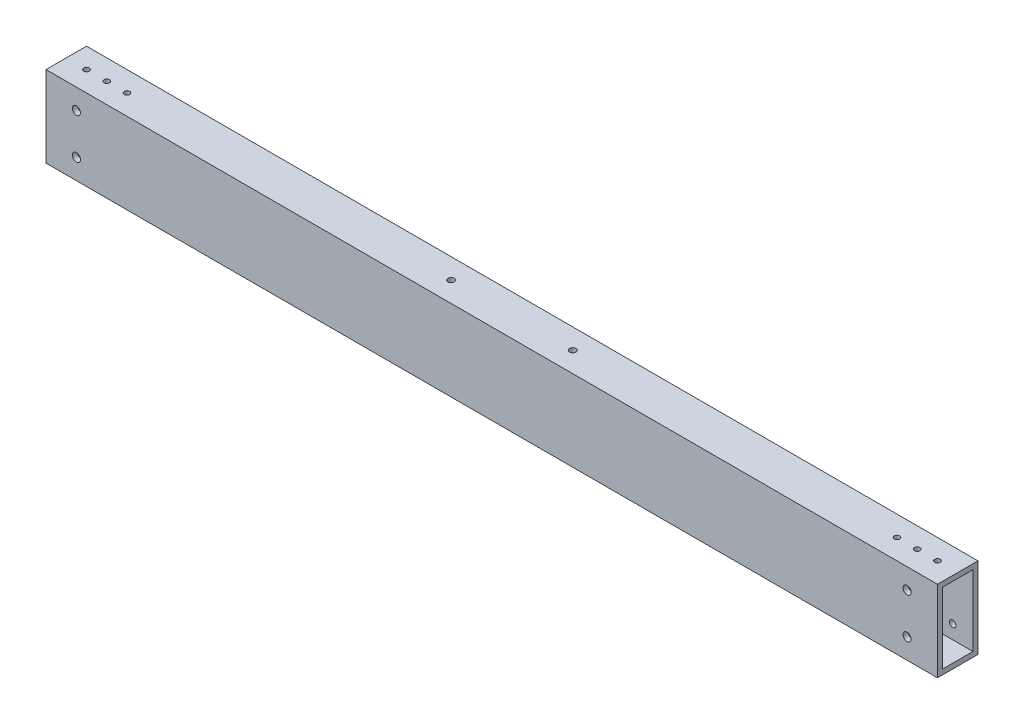
SolidWorks part; units mm, degrees
material "6061-T6 (SS)"
ref_plane "Front Plane" through (0, 0, 0) normal (0, 0, 1) x (1, 0, 0)
ref_plane "Top Plane" through (0, 0, 0) normal (0, 1, 0) x (1, 0, 0)
ref_plane "Right Plane" through (0, 0, 0) normal (1, 0, 0) x (0, 0, -1)
sketch "Sketch1" plane through (0, 0, 0) normal (0, 0, 1) x (1, 0, 0)
  line L1 (-279.4, 25.4) -> (279.4, 25.4)
  line L2 (-279.4, 25.4) -> (-279.4, -25.4)
  line L3 (-279.4, -25.4) -> (279.4, -25.4)
  line L4 (279.4, 25.4) -> (279.4, -25.4)
  line L5 (-279.4, 25.4) -> (279.4, -25.4) construction
  line L6 (-279.4, -25.4) -> (279.4, 25.4) construction
  point P0 (0, 0)
  dimension "D1" = 50.8
  dimension "D2" = 558.8
extrude "Boss-Extrude1" add sketch "Sketch1" along normal mid plane 25.4
sketch "Sketch2" plane through (279.4, 0, 0) normal (1, 0, 0) x (0, 0, -1)
  line L8 (9.525, -22.225) -> (9.525, 22.225)
  line L9 (9.525, 22.225) -> (-9.525, 22.225)
  line L10 (-9.525, 22.225) -> (-9.525, -22.225)
  line L11 (-9.525, -22.225) -> (9.525, -22.225)
  line L12 (9.525, -22.225) -> (9.525, 22.225)
  line L13 (9.525, 22.225) -> (-9.525, 22.225)
  line L14 (-9.525, 22.225) -> (-9.525, -22.225)
  line L15 (-9.525, -22.225) -> (9.525, -22.225)
  dimension "D1" = 3.175
extrude "Cut-Extrude1" cut sketch "Sketch2" against normal through all
sketch "Sketch3" plane through (0, 0, 12.7) normal (0, 0, 1) x (1, 0, 0)
sketch "Sketch4" plane through (0, 25.4, 0) normal (0, 1, 0) x (1, 0, 0)
  line L0 (-279.4, -12.7) -> (-279.4, 12.7) construction
  line L1 (0, -12.7) -> (0, 12.7) construction
  line L2 (279.4, -12.7) -> (-279.4, -12.7) construction
  line L3 (279.4, 12.7) -> (-279.4, 12.7) construction
  circle A0 centre (-304.8, 0) radius 1.7272
  circle A1 centre (-292.1, 0) radius 1.7272
  circle A3 centre (-266.7, 0) radius 1.7272
  circle A4 centre (-254, 0) radius 1.7272
  circle A5 centre (-241.3, 0) radius 1.7272
  circle A7 centre (241.3, 0) radius 1.7272
  circle A8 centre (254, 0) radius 1.7272
  circle A9 centre (266.7, 0) radius 1.7272
  circle A12 centre (-279.4, 0) radius 1.7272 [skipped]
  circle A14 centre (-228.6, 0) radius 1.7272 [skipped]
  dimension "D2" = 3.4544
  dimension "D3" = 7
  dimension "D4" = 12.7
extrude "Cut-Extrude2" cut sketch "Sketch4" against normal blind 6.35
hole_wizard "1/4-20 Tapped Hole1" positions "Sketch8" profile "Sketch7" tap size "1/4-20" standard "ANSI Inch"
sketch "Sketch8" plane through (0, 0, 12.7) normal (0, 0, 1) x (1, 0, 0)
  line L0 (-279.4, 25.4) -> (-279.4, -25.4) construction
  line L1 (279.4, -25.4) -> (279.4, 25.4) construction
  line L2 (-279.4, -25.4) -> (279.4, -25.4) construction
  point P0 (-260.35, 12.7)
  point P2 (-260.35, -12.7)
  point P4 (260.35, 12.7)
  point P6 (260.35, -12.7)
  dimension "D1" = 25.4
  dimension "D2" = 19.05
  dimension "D3" = 25.4
  dimension "D4" = 19.05
  dimension "D5" = 12.7
  dimension "D6" = 12.7
sketch "Sketch7" plane through (-260.35, 12.7, 12.7) normal (1, 0, 0) x (0, -1, 0)
  line L0 (0, 0) -> (0, 6.6138)
  line L1 (0, 6.6138) -> (2.5527, 5.08)
  line L2 (2.5527, 5.08) -> (2.5527, 0)
  line L5 (2.5527, 0) -> (0, 0)
  line L10 (0, 6.6138) -> (-2.5527, 5.08) construction
  line L11 (0, -6.35) -> (0, 107.95) construction
  dimension "Tap Drill Dia." = 5.1054
  dimension "Tap Drill Depth" = 5.08
  dimension "Drill Angle" = 118
hole_wizard "#10-32 Tapped Hole1" positions "Sketch10" profile "Sketch9" tap size "#10-32" standard "ANSI Inch"
sketch "Sketch10" plane through (0, 0, -12.7) normal (0, 0, -1) x (-1, 0, 0)
  line L0 (-279.4, 25.4) -> (279.4, 25.4) construction
  line L1 (-279.4, -25.4) -> (-279.4, 25.4) construction
  point P0 (-266.7, -13.4937)
  point P15 (-190.5, -13.4937)
  point P16 (-114.3, -13.4937)
  point P17 (-38.1, -13.4937)
  point P18 (38.1, -13.4937)
  point P19 (114.3, -13.4937)
  point P20 (190.5, -13.4937)
  point P21 (266.7, -13.4937)
  dimension "D1" = 76.2
  dimension "D2" = 38.8937
  dimension "D3" = 12.7
  dimension "D5" = 8
sketch "Sketch9" plane through (266.7, -13.4937, -12.7) normal (1, 0, 0) x (0, 1, 0)
  line L0 (0, 0) -> (0, 6.2933)
  line L1 (0, 6.2933) -> (2.0193, 5.08)
  line L2 (2.0193, 5.08) -> (2.0193, 0)
  line L5 (2.0193, 0) -> (0, 0)
  line L10 (0, 6.2933) -> (-2.0193, 5.08) construction
  line L11 (0, -6.35) -> (0, 107.95) construction
  dimension "Tap Drill Dia." = 4.0386
  dimension "Tap Drill Depth" = 5.08
  dimension "Drill Angle" = 118
hole_wizard "5/32 (0.15625) Diameter Hole1" positions "Sketch12" profile "Sketch11" hole size "5/32" standard "ANSI Inch" end condition through all
sketch "Sketch12" plane through (0, 25.4, 0) normal (0, 1, 0) x (1, 0, 0)
  line L2 (-38.1, 0) -> (38.1, 0) construction
  point P0 (-38.1, 0)
  point P2 (38.1, 0)
  dimension "D1" = 76.2
sketch "Sketch11" plane through (-38.1, 25.4, 0) normal (1, 0, 0) x (0, 0, 1)
  line L0 (0, 0) -> (0, 50.8)
  line L1 (0, 50.8) -> (1.9844, 50.8)
  line L2 (1.9844, 50.8) -> (1.9844, 0)
  line L5 (1.9844, 0) -> (0, 0)
  line L11 (0, -6.35) -> (0, 107.95) construction
  dimension "Thru Hole Dia." = 3.9688
  dimension "Thru Hole Depth" = 50.8
